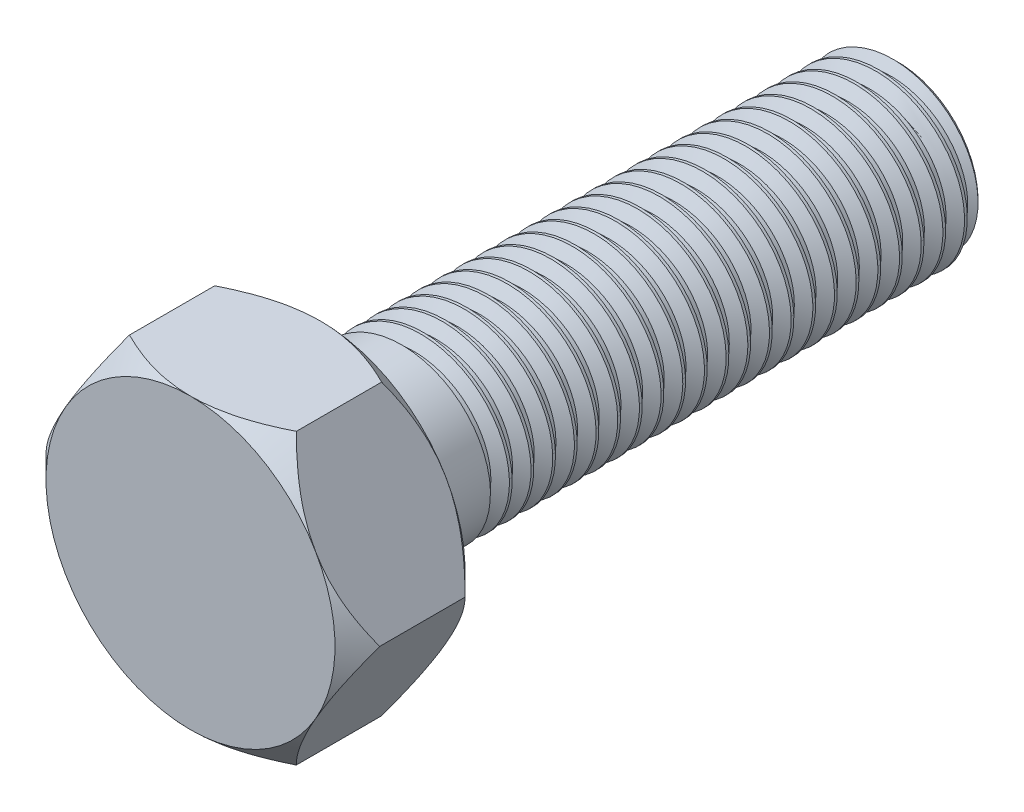
SolidWorks part; units mm, degrees
ref_plane "Front Plane" through (0, 0, 0) normal (0, 0, 1) x (1, 0, 0)
ref_plane "Top Plane" through (0, 0, 0) normal (0, 1, 0) x (1, 0, 0)
ref_plane "Right Plane" through (0, 0, 0) normal (1, 0, 0) x (0, 0, -1)
sketch "Sketch1" plane through (0, 0, 0) normal (0, 0, 1) x (1, 0, 0)
  line L1 (-11.547, 0) -> (-5.7735, -10)
  line L2 (-5.7735, -10) -> (5.7735, -10)
  line L3 (5.7735, -10) -> (11.547, 0)
  line L4 (11.547, 0) -> (5.7735, 10)
  line L5 (5.7735, 10) -> (-5.7735, 10)
  line L6 (-5.7735, 10) -> (-11.547, 0)
  circle A0 centre (0, 0) radius 10 construction
  dimension "D1" = 20
extrude "Boss-Extrude1" add sketch "Sketch1" along normal mid plane 9
sketch "Sketch2" plane through (0, 0, 4.5) normal (0, 0, 1) x (1, 0, 0)
  line L0 (-5.7735, 10) -> (-11.547, 0) construction
  circle A0 centre (0, 0) radius 10
extrude "Cut-Extrude1" cut sketch "Sketch2" against normal through all draft 45 flip side to cut
mirror "Mirror1" about plane through (0, 0, 0) normal (0, 0, 1) of "Cut-Extrude1"
sketch "Sketch4" plane through (0, 0, -4.5) normal (0, 0, -1) x (-1, 0, 0)
  circle A0 centre (0, 0) radius 6
  dimension "D1" = 12
extrude "Boss-Extrude2" add sketch "Sketch4" along normal blind 40
chamfer "Chamfer2" distance 0.5 angle 45 1 edges at (-6, 0, -44.5)
thread "Thread1" pitch 1.5 method cut profile "Thread Profile1" start angle 0, offset 5, length 0, pitch 1.5, diameter 12
ref_plane "Plane1" through (-6, 0, -9.5) normal (0, -1, 0) x (-1, 0, 0)
sketch "Thread Profile1" plane through (-6, 0, -9.5) normal (0, -1, 0) x (-1, 0, 0)
  line L0 (0, 0) -> (0, 1.5) construction
  line L11 (0, 0) -> (0, 1.3125)
  line L12 (0, 1.3125) -> (-0.8119, 0.8437)
  line L13 (-0.8119, 0.8437) -> (-0.8119, 0.4687)
  line L15 (-0.8119, 0.4687) -> (0, 0)
  line L17 (-0.8119, 0.6562) -> (0, 0.6562) construction
  point P2 (0, 0)
  dimension "Pitch" = 1.5
  dimension "Profile_Angle" = 60
  dimension "Profile_Land" = 0.375
  dimension "Profile_Height" = 0.8119
sketch "Sketch10" plane through (0, 0, 0) normal (0, 1, 0) x (1, 0, 0)
  line L4 (-6, 9.5) -> (-5.1881, 9.9687)
  line L5 (-5.1881, 9.9687) -> (-5.1881, 10.3437)
  line L6 (-5.1881, 10.3437) -> (-6, 10.8125)
  line L7 (-6, 10.8125) -> (-6, 9.5)
  line L8 (-6, 9.5) -> (-5.1881, 9.9687)
  line L9 (-5.1881, 9.9687) -> (-5.1881, 10.3437)
  line L10 (-5.1881, 10.3437) -> (-6, 10.8125)
  line L11 (-6, 10.8125) -> (-6, 9.5)
  dimension "D1" = 0
extrude "Cut-Extrude2" cut sketch "Sketch10" against normal through all
